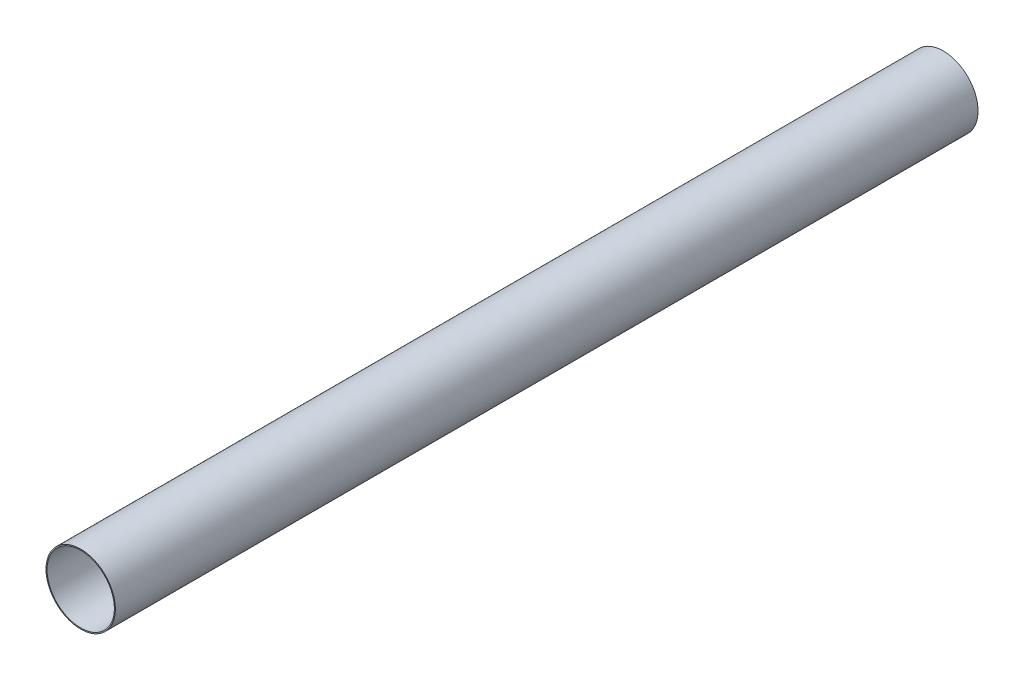
SolidWorks part; units mm, degrees
ref_plane "Front Plane" through (0, 0, 0) normal (0, 0, 1) x (1, 0, 0)
ref_plane "Top Plane" through (0, 0, 0) normal (0, 1, 0) x (1, 0, 0)
ref_plane "Right Plane" through (0, 0, 0) normal (1, 0, 0) x (0, 0, -1)
sketch "Sketch1" plane through (0, 0, 0) normal (0, 0, 1) x (1, 0, 0)
  circle A0 centre (0, 0) radius 49.53
  circle A1 centre (0, 0) radius 51.054
  dimension "D1" = 99.06
  dimension "D2" = 102.108
extrude "Boss-Extrude1" add sketch "Sketch1" along normal blind 1270
